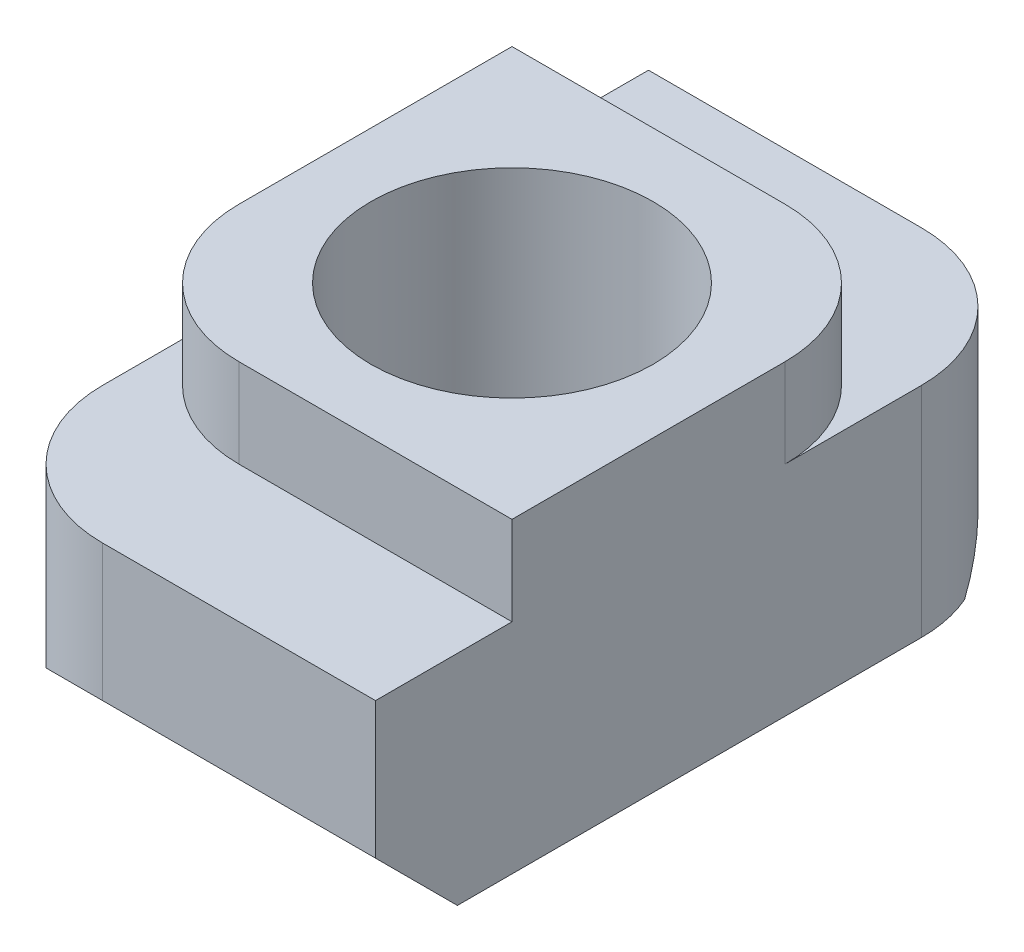
SolidWorks part; units mm, degrees
ref_plane "Front Plane" through (0, 0, 0) normal (0, 0, 1) x (1, 0, 0)
ref_plane "Top Plane" through (0, 0, 0) normal (0, 1, 0) x (1, 0, 0)
ref_plane "Right Plane" through (0, 0, 0) normal (1, 0, 0) x (0, 0, -1)
ref_axis "Axis_X" through (-3.3, 0, 0) along (1, 0, 0)
ref_axis "Axis_Y" through (0, 0.225, 0) along (0, -1, 0)
ref_axis "Axis_Z" through (0, 0, -5.5) along (0, 0, 1)
sketch "Sketch1" plane through (0, 0, 0) normal (1, 0, 0) x (0, 0, -1)
  line L0 (-3, 0) -> (3, 0)
  line L1 (3, 0) -> (3, -1.3)
  line L2 (3, -1.3) -> (5, -1.3)
  line L3 (5, -1.3) -> (5, -3.3)
  line L4 (5, -3.3) -> (3.8, -4.5)
  line L5 (3.8, -4.5) -> (-3.8, -4.5)
  line L6 (-3.8, -4.5) -> (-5, -3.3)
  line L7 (-5, -3.3) -> (-5, -1.3)
  line L8 (-5, -1.3) -> (-3, -1.3)
  line L9 (-3, -1.3) -> (-3, 0)
  line L10 (0, 0) -> (0, -4.5) construction
  dimension "FIX_1" = 45
  dimension "FIX_2" = 10
  dimension "FIX_3" = 6
  dimension "FIX_4" = 3.2
  dimension "FIX_5" = 2
  dimension "FIX_6" = 4.5
extrude "Boss-Extrude1" add sketch "Sketch1" along normal mid plane 6
fillet "Fillet1" radius 2 4 edges at (3, -2.3, -5) (-3, -2.3, 5) (3, -0.65, -3) (-3, -0.65, 3)
hole_wizard "Tap1" positions "Sketch3" profile "Sketch2" hole size "M3x0.5" standard "JIS" end condition through all
sketch "Sketch3" plane through (0, 0, 0) normal (0, 1, 0) x (1, 0, 0)
  point P0 (0, 0)
sketch "Sketch2" plane through (0, 0, 0) normal (1, 0, 0) x (0, 0, 1)
  line L0 (0, 0) -> (0, 4.5)
  line L1 (0, 4.5) -> (2.067, 4.5)
  line L2 (2.067, 4.5) -> (2.067, 0)
  line L5 (2.067, 0) -> (0, 0)
  line L11 (0, -6.35) -> (0, 107.95) construction
  dimension "FIX_9" = 4.134
  dimension "Thru Hole Depth" = 4.5
cosmetic thread "Thread1" parameters "FIX_10"=5
equation "\"Factor\"= 1.082532"
